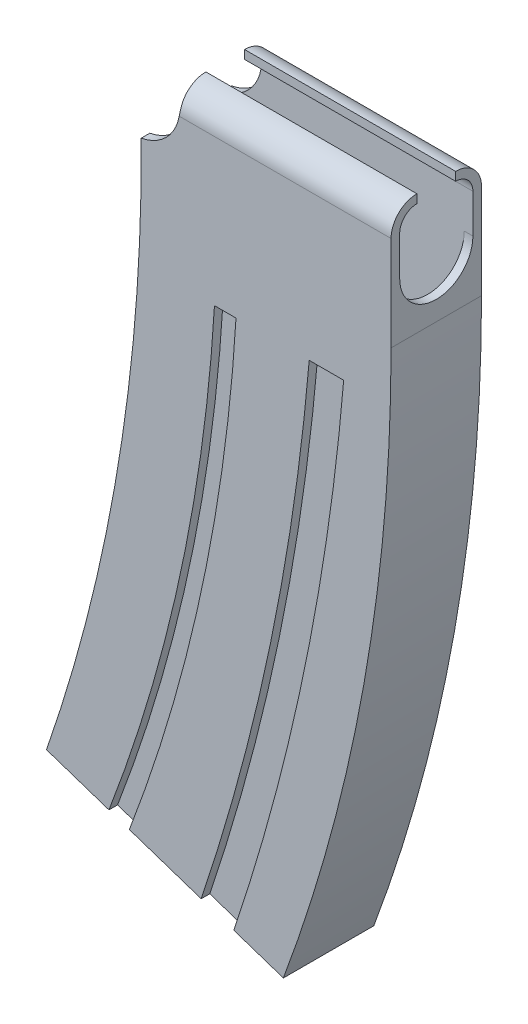
SolidWorks part; units mm, degrees
ref_plane "前视基准面" through (0, 0, 0) normal (0, 0, 1) x (1, 0, 0)
ref_plane "上视基准面" through (0, 0, 0) normal (0, 1, 0) x (1, 0, 0)
ref_plane "右视基准面" through (0, 0, 0) normal (1, 0, 0) x (0, 0, -1)
other "Configuration Table"
sketch "草图2" plane through (0, 0, 0) normal (0, 0, 1) x (1, 0, 0)
  line L0 (-49, 0) -> (0, 0)
  line L1 (0, 0) -> (0, -28)
  line L2 (-25, -167.1941) -> (-80, -148.7914)
  line L3 (-49, 0) -> (-49, -4)
  arc A0 (0, -28) -> (-25, -167.1941) centre (-400, -28) cw
  arc A1 (-49, -4) -> (-58, -14.8167) centre (-60, -4) cw
  arc A3 (-58, -14.8167) -> (-80, -148.7914) centre (-457.9879, -17.9283) cw
  dimension "D4" = 11
  dimension "D6" = 400
  dimension "D7" = 18.5
  dimension "D10" = 400
  dimension "D1" = 49
  dimension "D2" = 4
  dimension "D3" = 58
  dimension "D5" = 28
  dimension "D8" = 25
  dimension "D9" = 55
extrude "凸台-拉伸1" add sketch "草图2" along normal mid plane 21 contours A3 L2 A0 L1 L0 L3 A1
sketch "草图4" plane through (0, 0, 10.5) normal (0, 0, 1) x (1, 0, 0)
  line L0 (-41, -40) -> (-36, -40)
  line L1 (-25, -167.1941) -> (-80, -148.7914) construction
  line L2 (-65.5, -153.643) -> (-60.7584, -155.2295)
  line L3 (-44.0866, -160.8078) -> (-36.5, -163.3463)
  line L4 (-19, -40) -> (-11, -40)
  line L5 (0, 0) -> (0, -28) construction
  line L6 (-49, 0) -> (0, 0) construction
  arc A0 (-41, -40) -> (-65.5, -153.643) centre (-421.3331, -17.4674) cw
  arc A1 (-36, -40) -> (-60.7584, -155.2295) centre (-423.3209, -17.0542) cw
  arc A2 (-19, -40) -> (-44.0866, -160.8078) centre (-537.0859, 4.5755) cw
  arc A3 (-11, -40) -> (-36.5, -163.3463) centre (-537.1248, 4.4595) cw
  point P14 (0, 0)
  point P16 (-0.0906, -36.5146)
  dimension "D6" = 381
  dimension "D7" = 388
  dimension "D8" = 520
  dimension "D9" = 528
  dimension "D1" = 5
  dimension "D2" = 8
  dimension "D3" = 11
  dimension "D4" = 36
  dimension "D5" = 40
  dimension "D10" = 16.5
  dimension "D11" = 36.5
extrude "切除-拉伸3" cut sketch "草图4" against normal blind 2
extrude "切除-拉伸4" cut sketch "草图4<3>" along normal blind 2 from surface starting at face at (-35.3026, -52.3548, -10.5)
sketch "草图4<3>" plane through (0, 0, 10.5) normal (0, 0, 1) x (1, 0, 0) same geometry as "草图4"
fillet "圆角2" radius 6 2 edges at (-24.5, 0, -10.5) (-24.5, 0, 10.5)
shell "抽壳1" thickness 2 removed face at (-51.6045, -8.7288, 0.0572) removed face at (-49, -1.5505, 0)
sketch "草图9" plane through (0, 0, 0) normal (1, 0, 0) x (0, 0, -1)
  line L4 (-4.5, -2) -> (-4.5, 0)
  line L5 (4.5, -2) -> (4.5, 0)
  line L7 (-4.5, 0) -> (4.5, 0) construction
  line L8 (8.5, -26) -> (8.5, -6)
  line L9 (4.5, -2) -> (-4.5, -2)
  line L10 (-8.5, -6) -> (-8.5, -26)
  line L11 (-8.5, -26) -> (8.5, -26)
  line L12 (8.5, -15) -> (8.5, -6)
  line L14 (-8.5, -6) -> (-8.5, -15)
  line L16 (-4.5, 0) -> (4.5, 0)
  arc A3 (-8.5, -15) -> (8.5, -15) centre (0, -15) ccw
  arc A4 (8.5, -6) -> (4.5, -2) centre (4.5, -6) ccw
  arc A5 (-4.5, -2) -> (-8.5, -6) centre (-4.5, -6) ccw
  arc A6 (8.5, -6) -> (4.5, -2) centre (4.5, -6) ccw
  arc A7 (-4.5, -2) -> (-8.5, -6) centre (-4.5, -6) ccw
  dimension "D2" = 15
  dimension "D1" = 2
extrude "切除-拉伸5" cut sketch "草图9" against normal through all
